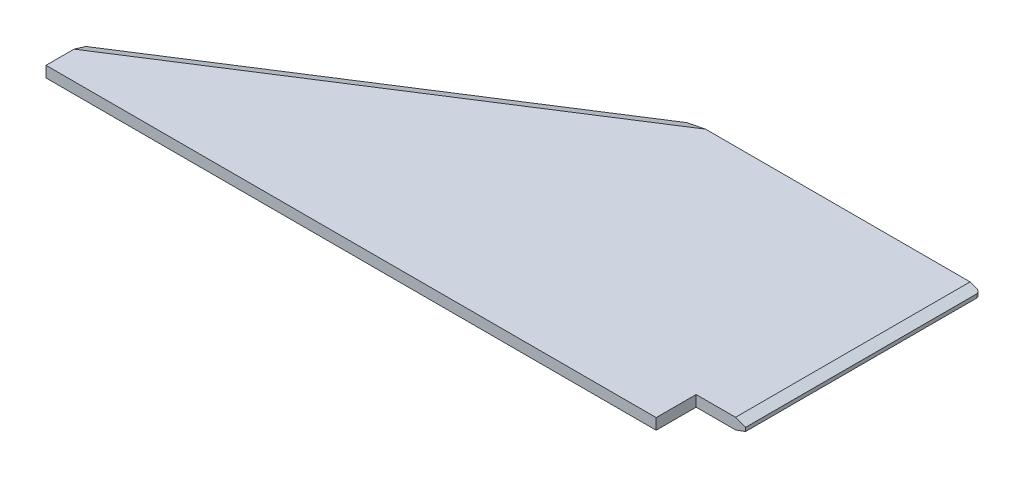
SolidWorks part; units mm, degrees
material "A-Glass Fiber"
ref_plane "Front Plane" through (0, 0, 0) normal (0, 0, 1) x (1, 0, 0)
ref_plane "Top Plane" through (0, 0, 0) normal (0, 1, 0) x (1, 0, 0)
ref_plane "Right Plane" through (0, 0, 0) normal (1, 0, 0) x (0, 0, -1)
sketch "Sketch1" plane through (0, 0, 0) normal (0, 1, 0) x (1, 0, 0)
  line L0 (0, 0) -> (0, 10.9)
  line L1 (0, 10.9) -> (100, 74.9)
  line L2 (100, 74.9) -> (180, 74.9)
  line L3 (180, 74.9) -> (180, 10.9)
  line L7 (180, 10.9) -> (166.5, 10.9)
  line L9 (166.5, 0) -> (0, 0)
  line L10 (-989.0676, -29) -> (49010.9324, -29) construction
  line L11 (-1000, 0) -> (49000, 0) construction
  line L12 (-999.3384, -58) -> (49000.6616, -58) construction
  line L13 (0, 0) -> (0, -58) construction
  line L15 (166.5, 0) -> (166.5, 10.9)
  point P15 (0, -29)
  dimension "D1" = 80
  dimension "D2" = 180
  dimension "D3" = 13.5
  dimension "D4" = 100
  dimension "D5" = 64
  dimension "D6" = 79.8
  dimension "D7" = 58
extrude "Boss-Extrude1" add sketch "Sketch1" along normal blind 3
chamfer "Chamfer1" distance 1 angle 70 2 edges at (180, 3, -42.9) (50, 3, -42.9) first distance on face at (180, 1.5, -42.9) first distance on face at (50, 1.5, -42.9)
chamfer "Chamfer2" distance 1 angle 70 2 edges at (50, 0, -42.9) (180, 0, -42.9) first distance on face at (50, 1, -42.9) first distance on face at (180, 1, -42.9)
fillet "Fillet1" radius 1 1 edges at (180, 1.5, -74.9)
